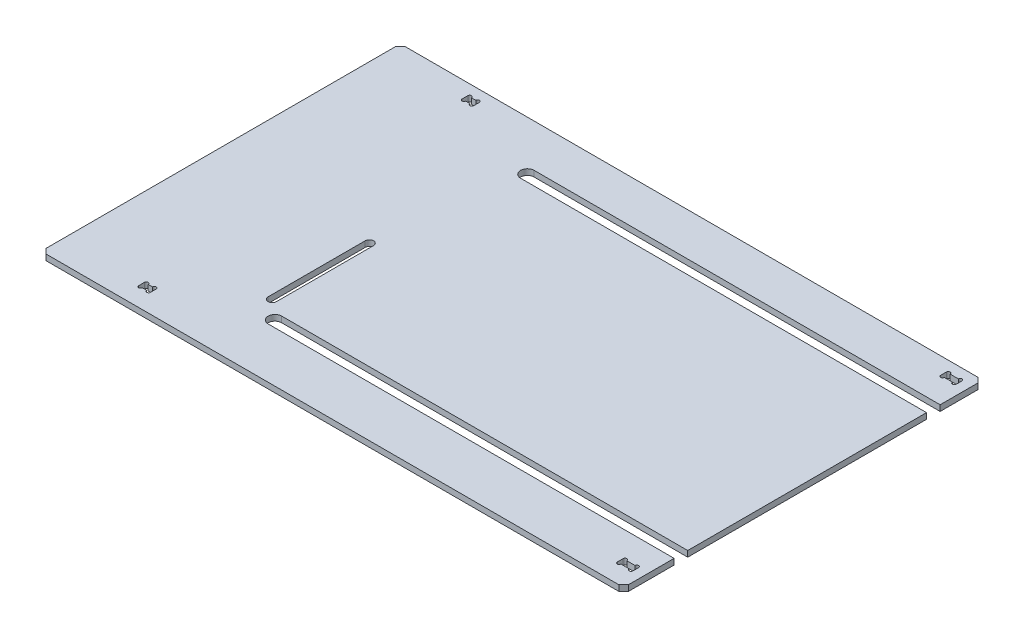
SolidWorks part; units mm, degrees
ref_plane "정면" through (0, 0, 0) normal (0, 0, 1) x (1, 0, 0)
ref_plane "윗면" through (0, 0, 0) normal (0, 1, 0) x (1, 0, 0)
ref_plane "우측면" through (0, 0, 0) normal (1, 0, 0) x (0, 0, -1)
sketch "스케치1" plane through (0, 0, 0) normal (0, 1, 0) x (1, 0, 0)
  line L1 (0, 0) -> (300, 0)
  line L2 (0, 0) -> (0, 185)
  line L3 (0, 185) -> (300, 185)
  line L4 (300, 0) -> (300, 185)
  dimension "D1" = 185
  dimension "D2" = 300
extrude "보스-돌출1" add sketch "스케치1" along normal blind 3
sketch "스케치2" plane through (0, 3, 0) normal (0, 1, 0) x (1, 0, 0)
  line L0 (92.9, 63.1066) -> (93.0904, 63.1066) construction
  line L1 (92.9, 60.6066) -> (92.9, 65.6066) construction
  line L3 (78.8, 63.1066) -> (78.8, 88.1066)
  line L4 (78.8, 38.1066) -> (83.1, 38.1066)
  line L5 (78.8, 38.1066) -> (78.8, 63.1066)
  line L6 (78.8, 88.1066) -> (83.1, 88.1066)
  line L7 (83.1, 38.1066) -> (83.1, 88.1066)
  line L8 (80, 83.2292) -> (80, 85.4866) construction
  line L10 (80.9, 83.2292) -> (80.9, 85.4866) construction
  dimension "D1" = 1.2
  dimension "D2" = 2.2
  dimension "D3" = 25
  dimension "D4" = 25
extrude "컷-돌출1" cut sketch "스케치2" against normal blind 10
sketch "스케치3" plane through (0, 3, 0) normal (0, 1, 0) x (1, 0, 0)
  line L0 (83.1, 88.1066) -> (78.8, 88.1066) construction
  line L1 (78.8, 38.1066) -> (83.1, 38.1066) construction
  circle A0 centre (80.95, 88.1066) radius 2.15
  circle A1 centre (80.95, 38.1066) radius 2.15
extrude "컷-돌출2" cut sketch "스케치3" against normal blind 10
sketch "스케치4" plane through (0, 3, 0) normal (0, 1, 0) x (1, 0, 0)
  line L0 (262.6559, 162) -> (279.5163, 162) construction
  line L1 (300, 163) -> (90.9, 163)
  line L2 (300, 163) -> (300, 156)
  line L3 (300, 156) -> (90.9, 156)
  line L4 (90.9, 163) -> (90.9, 156)
  line L5 (90.9, 26) -> (300, 26)
  line L6 (90.9, 26) -> (90.9, 33)
  line L7 (90.9, 33) -> (300, 33)
  line L8 (300, 26) -> (300, 33)
  line L9 (262.6559, 157) -> (279.5163, 157) construction
  line L10 (262.6559, 32) -> (279.5163, 32) construction
  line L13 (300, 0) -> (300, 185) construction
  dimension "D1" = 1
  dimension "D2" = 1
  dimension "D3" = 1
  dimension "D4" = 10
extrude "컷-돌출3" cut sketch "스케치4" against normal blind 10
sketch "스케치5" plane through (0, 3, 0) normal (0, 1, 0) x (1, 0, 0)
  line L0 (90.9, 163) -> (90.9, 156) construction
  line L3 (90.9, 33) -> (90.9, 26) construction
  circle A0 centre (90.9, 159.5) radius 3.5
  circle A3 centre (90.9, 29.5) radius 3.5
extrude "컷-돌출5" cut sketch "스케치5" against normal blind 10
chamfer "모따기1" distance 2.5 angle 45 4 edges at (0, 1.5, 0) (0, 1.5, -185) (300, 1.5, 0) (300, 1.5, -185)
sketch "스케치6" plane through (0, 0, 0) normal (0, -1, 0) x (1, 0, 0)
  line L0 (295, -179.5) -> (295, -9.5) construction
  line L1 (46.5, -179.25) -> (40.5, -179.25)
  line L2 (46.5, -179.25) -> (46.5, -176.25)
  line L3 (46.5, -176.25) -> (40.5, -176.25)
  line L4 (40.5, -179.25) -> (40.5, -176.25)
  line L5 (287, -176.25) -> (295, -176.25)
  line L6 (287, -176.25) -> (287, -179.25)
  line L7 (287, -179.25) -> (295, -179.25)
  line L8 (295, -176.25) -> (295, -179.25)
  line L9 (300, -94.5) -> (244.3606, -94.5) construction
  line L10 (300, -33) -> (300, -156) construction
  line L11 (295, -12.75) -> (295, -9.75)
  line L12 (287, -9.75) -> (295, -9.75)
  line L13 (287, -12.75) -> (287, -9.75)
  line L14 (287, -12.75) -> (295, -12.75)
  line L15 (40.5, -9.75) -> (40.5, -12.75)
  line L16 (46.5, -12.75) -> (40.5, -12.75)
  line L17 (46.5, -9.75) -> (46.5, -12.75)
  line L18 (46.5, -9.75) -> (40.5, -9.75)
  dimension "D1" = 6
  dimension "D2" = 3
  dimension "D3" = 3
extrude "컷-돌출6" cut sketch "스케치6" against normal blind 3
sketch "스케치7" plane through (0, 3, 0) normal (0, 1, 0) x (1, 0, 0)
  line L0 (40.5, 12.75) -> (46.5, 12.75) construction
  line L1 (46.5, 9.75) -> (40.5, 9.75) construction
  line L2 (295, 9.75) -> (287, 9.75) construction
  line L3 (287, 12.75) -> (295, 12.75) construction
  line L4 (23.5484, 94.5) -> (300, 94.5) construction
  line L7 (300, 33) -> (300, 156) construction
  circle A0 centre (41.4422, 12.75) radius 0.9422
  circle A1 centre (45.5578, 12.75) radius 0.9422
  circle A2 centre (45.5578, 9.75) radius 0.9422
  circle A3 centre (41.4422, 9.75) radius 0.9422
  circle A4 centre (294.0578, 9.75) radius 0.9422
  circle A5 centre (294.0578, 12.75) radius 0.9422
  circle A6 centre (287.9422, 12.75) radius 0.9422
  circle A7 centre (287.9422, 9.75) radius 0.9422
  circle A8 centre (287.9422, 179.25) radius 0.9422
  circle A9 centre (287.9422, 176.25) radius 0.9422
  circle A10 centre (294.0578, 176.25) radius 0.9422
  circle A11 centre (294.0578, 179.25) radius 0.9422
  circle A12 centre (41.4422, 179.25) radius 0.9422
  circle A13 centre (45.5578, 179.25) radius 0.9422
  circle A14 centre (45.5578, 176.25) radius 0.9422
  circle A15 centre (41.4422, 176.25) radius 0.9422
  point P36 (300, 94.5)
extrude "컷-돌출7" cut sketch "스케치7" against normal blind 10
